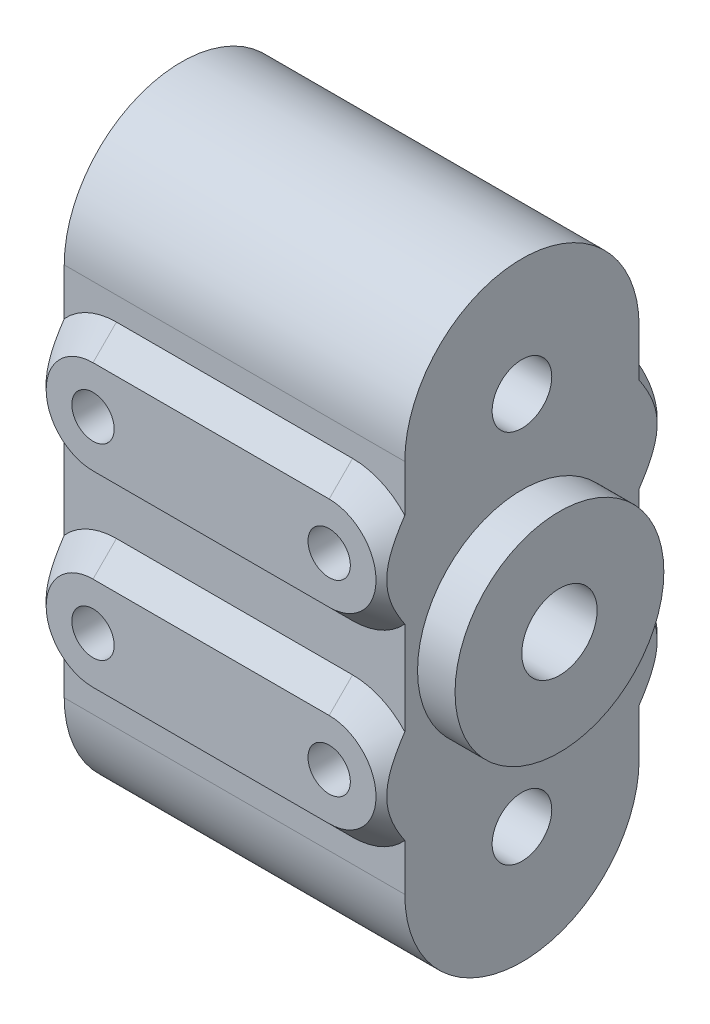
SolidWorks part; units mm, degrees
material "PET"
ref_plane "Front" through (0, 0, 0) normal (0, 0, 1) x (1, 0, 0)
ref_plane "Top" through (0, 0, 0) normal (0, 1, 0) x (1, 0, 0)
ref_plane "Right" through (0, 0, 0) normal (1, 0, 0) x (0, 0, -1)
sketch "Sketch1" plane through (0, 0, 0) normal (1, 0, 0) x (0, 0, -1)
  line L0 (0, 12.7) -> (0, -12.7) construction
  line L1 (7.9375, 12.7) -> (7.9375, -12.7)
  line L2 (-7.9375, 12.7) -> (-7.9375, -12.7)
  arc A0 (7.9375, 12.7) -> (-7.9375, 12.7) centre (0, 12.7) ccw
  arc A1 (-7.9375, -12.7) -> (7.9375, -12.7) centre (0, -12.7) ccw
  point P2 (0, 0)
  dimension "D1" = 15.875
  dimension "D2" = 25.4
extrude "Boss-Extrude1" add sketch "Sketch1" along normal blind 23.075
sketch "Sketch8" plane through (23.075, 0, 0) normal (1, 0, 0) x (0, 0, -1)
  circle A0 centre (0, 0) radius 7.0739
  dimension "D1" = 14.1478
extrude "Boss-Extrude2" add sketch "Sketch8" along normal blind 2.54
hole_wizard "1/4-20 Tapped Hole1" positions "Sketch9" profile "Sketch10" tap size "1/4-20" standard "ANSI Inch" end condition through all
sketch "Sketch9" plane through (25.615, 0, 0) normal (1, 0, 0) x (0, 0, -1)
  point P0 (0, 0)
sketch "Sketch10" plane through (25.615, 0, 0) normal (0, 1, 0) x (0, 0, -1)
  line L0 (0, 0) -> (0, 25.615)
  line L1 (0, 25.615) -> (2.5527, 25.615)
  line L2 (2.5527, 25.615) -> (2.5527, 0)
  line L5 (2.5527, 0) -> (0, 0)
  line L11 (0, -6.35) -> (0, 107.95) construction
  dimension "Thru Tap Drill Dia." = 5.1054
  dimension "Thru Tap Drill Depth" = 25.615
cosmetic thread "Hole Thread8" parameters "D2"=6.35
hole_wizard "#10-32 Tapped Hole1" positions "Sketch4" profile "Sketch5" tap size "#10-32" standard "ANSI Inch" end condition through all
sketch "Sketch4" plane through (23.075, 0, 0) normal (1, 0, 0) x (0, 0, -1)
  point P0 (0, 12.7)
  point P2 (0, -12.7)
sketch "Sketch5" plane through (23.075, 12.7, 0) normal (0, 1, 0) x (0, 0, -1)
  line L0 (0, 0) -> (0, 23.075)
  line L1 (0, 23.075) -> (2.0193, 23.075)
  line L2 (2.0193, 23.075) -> (2.0193, 0)
  line L5 (2.0193, 0) -> (0, 0)
  line L11 (0, -6.35) -> (0, 107.95) construction
  dimension "Thru Tap Drill Dia." = 4.0386
  dimension "Thru Tap Drill Depth" = 23.075
cosmetic thread "Hole Thread2" parameters "D2"=4.826
cosmetic thread "Hole Thread3" parameters "D2"=4.826
ref_plane "Plane1" through (0, 0, 9.525) normal (0, 0, 1) x (1, 0, 0)
sketch "Sketch13" plane through (0, 0, 9.525) normal (0, 0, 1) x (1, 0, 0)
  line L0 (3.5375, 6.35) -> (19.5375, 6.35) construction
  line L1 (3.5375, 9.525) -> (19.5375, 9.525)
  line L2 (3.5375, 3.175) -> (19.5375, 3.175)
  line L3 (0, 0) -> (3.6937, 0) construction
  line L4 (11.5375, 6.35) -> (11.5375, 20.6375) construction
  line L5 (23.075, 20.6375) -> (0, 20.6375) construction
  arc A0 (3.5375, 9.525) -> (3.5375, 3.175) centre (3.5375, 6.35) ccw
  arc A1 (19.5375, 3.175) -> (19.5375, 9.525) centre (19.5375, 6.35) ccw
  point P2 (11.5375, 6.35)
  dimension "D1" = 16
  dimension "D2" = 12.7
  dimension "D3" = 6.35
extrude "Boss-Extrude3" add sketch "Sketch13" against normal blind 2.54 draft 45 draft outward yes
mirror "Mirror1" about plane through (0, 0, 0) normal (0, 1, 0) of "Boss-Extrude3" second plane through (0, 0, 0) second plane normal (0, 0, 1)
sketch "Sketch14" plane through (0, 0, 0) normal (-1, 0, 0) x (0, 0, 1)
  line L1 (-9.525, 20.6375) -> (9.525, 20.6375)
  line L3 (-9.525, 20.6375) -> (-9.525, -20.6375)
  line L6 (-9.525, -20.6375) -> (9.525, -20.6375)
  line L7 (9.525, 20.6375) -> (9.525, -20.6375)
  line L8 (9.525, 3.175) -> (9.525, 9.525) construction
  line L9 (-9.525, 9.525) -> (-9.525, 3.175) construction
  arc A0 (7.9375, 12.7) -> (-7.9375, 12.7) centre (0, 12.7) ccw construction
  arc A1 (-7.9375, -12.7) -> (7.9375, -12.7) centre (0, -12.7) ccw construction
extrude "Cut-Extrude1" cut sketch "Sketch14" along normal through all
sketch "Sketch15" plane through (23.075, 0, 0) normal (1, 0, 0) x (0, 0, -1)
  line L4 (9.525, 20.6375) -> (-9.525, 20.6375)
  line L5 (-9.525, 20.6375) -> (-9.525, -20.6375)
  line L6 (-9.525, -20.6375) -> (9.525, -20.6375)
  line L7 (9.525, -20.6375) -> (9.525, 20.6375)
  line L8 (9.525, 20.6375) -> (-9.525, 20.6375)
  line L9 (-9.525, 20.6375) -> (-9.525, -20.6375)
  line L10 (-9.525, -20.6375) -> (9.525, -20.6375)
  line L11 (9.525, -20.6375) -> (9.525, 20.6375)
  circle A0 centre (0, 0) radius 7.0739 construction
  circle A1 centre (0, 0) radius 7.0739
  dimension "D1" = 0
extrude "Cut-Extrude2" cut sketch "Sketch15" along normal through all
hole_wizard "#6-40 Tapped Hole1" positions "Sketch6" profile "Sketch7" tap size "#6-40" standard "ANSI Inch" end condition through all
sketch "Sketch6" plane through (0, 0, 9.525) normal (0, 0, 1) x (1, 0, 0)
  point P0 (3.5375, 6.35)
  point P2 (19.5375, 6.35)
  point P4 (3.5375, -6.35)
  point P6 (19.5375, -6.35)
cosmetic thread "Hole Thread4" parameters "D2"=3.5052
cosmetic thread "Hole Thread5" parameters "D2"=3.5052
cosmetic thread "Hole Thread6" parameters "D2"=3.5052
cosmetic thread "Hole Thread7" parameters "D2"=3.5052
sketch "Sketch7" plane through (3.5375, 6.35, 9.525) normal (1, 0, 0) x (0, -1, 0)
  line L0 (0, 0) -> (0, 19.05)
  line L1 (0, 19.05) -> (1.4351, 19.05)
  line L2 (1.4351, 19.05) -> (1.4351, 0)
  line L5 (1.4351, 0) -> (0, 0)
  line L11 (0, -6.35) -> (0, 107.95) construction
  dimension "Thru Tap Drill Dia." = 2.8702
  dimension "Thru Tap Drill Depth" = 19.05
hole_wizard "13/64 (0.20313) Diameter Hole1" positions "Sketch11" profile "Sketch12" hole size "13/64" standard "ANSI Inch"
sketch "Sketch11" plane through (0, 0, 0) normal (-1, 0, 0) x (0, 0, 1)
  point P0 (0, -12.7)
  point P3 (0, 12.7)
sketch "Sketch12" plane through (0, -12.7, 0) normal (0, 1, 0) x (0, 0, 1)
  line L0 (0, 0) -> (0, 4.7251)
  line L1 (0, 4.7251) -> (2.5798, 3.175)
  line L2 (2.5798, 3.175) -> (2.5798, 0)
  line L5 (2.5798, 0) -> (0, 0)
  line L10 (0, 4.7251) -> (-2.5798, 3.175) construction
  line L11 (0, -6.35) -> (0, 107.95) construction
  dimension "Hole Dia." = 5.1595
  dimension "Hole Depth" = 3.175
  dimension "Drill Angle" = 118
